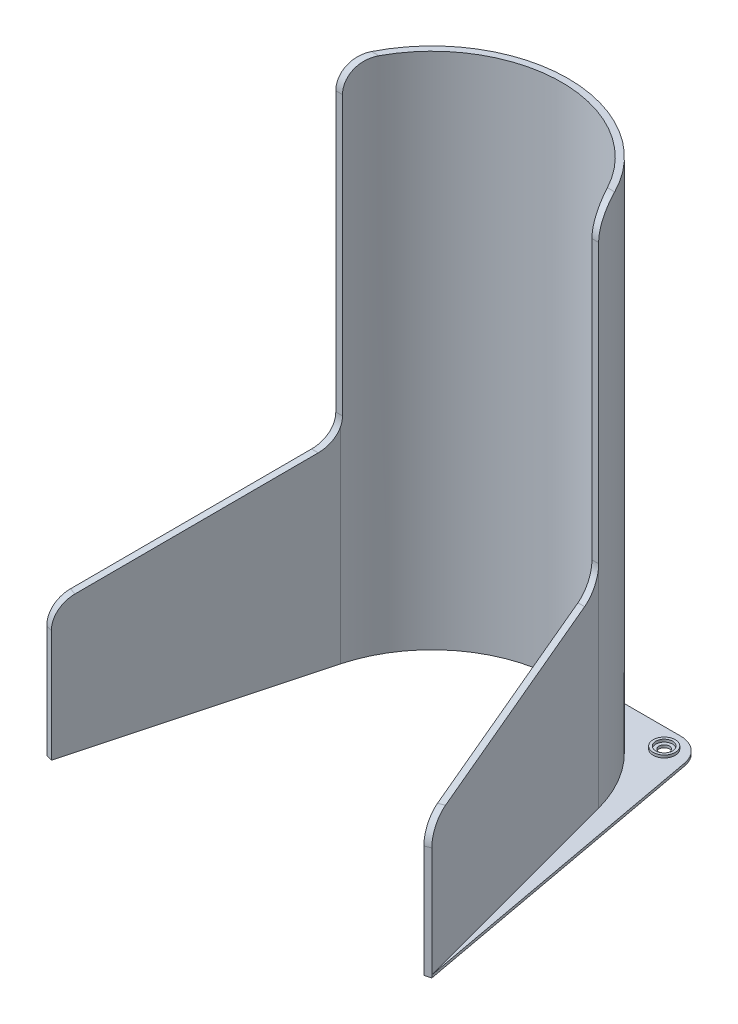
SolidWorks part; units mm, degrees
note: The reader was unsure of these and kept them because the rebuilt part matched: shared geometry of "Esquisse1<4>", "Esquisse1<6>".
ref_plane "Plan de face" through (0, 0, 0) normal (0, 0, 1) x (1, 0, 0)
ref_plane "Plan de dessus" through (0, 0, 0) normal (0, 1, 0) x (1, 0, 0)
ref_plane "Plan de droite" through (0, 0, 0) normal (1, 0, 0) x (0, 0, -1)
sketch "Esquisse1" plane through (0, 0, 0) normal (0, 1, 0) x (1, 0, 0)
  line L0 (0, 90) -> (0, 100) construction
  line L1 (-96.5926, 25.8819) -> (-143.72, -150)
  line L2 (143.72, -150) -> (-143.72, -150) construction
  line L3 (0, -150) -> (0, -100) construction
  line L4 (0, -90) -> (0, 0) construction
  line L5 (0, -100) -> (0, -90) construction
  line L6 (-143.72, -150) -> (-148.5496, -148.7059)
  line L7 (-148.5496, -148.7059) -> (-101.4222, 27.176)
  line L8 (0, 100) -> (0, 105) construction
  line L9 (-96.5926, 25.8819) -> (-101.4222, 27.176) construction
  line L10 (-148.5496, -148.7059) -> (-101.4222, 106.9873)
  line L11 (0, 105) -> (0, 106.9873) construction
  line L12 (-101.4222, 106.9873) -> (0, 0) construction
  line L13 (101.4222, 106.9873) -> (-101.4222, 106.9873)
  line L14 (-101.4222, 27.176) -> (-101.4222, 106.9873) construction
  line L15 (101.4222, 27.176) -> (101.4222, 106.9873) construction
  line L16 (101.4222, 106.9873) -> (0, 0) construction
  line L17 (148.5496, -148.7059) -> (101.4222, 106.9873)
  line L18 (148.5496, -148.7059) -> (101.4222, 27.176)
  line L19 (143.72, -150) -> (148.5496, -148.7059)
  line L20 (96.5926, 25.8819) -> (143.72, -150)
  arc A0 (0, 90) -> (0, -90) centre (0, 0) ccw construction
  arc A1 (96.5926, 25.8819) -> (-96.5926, 25.8819) centre (0, 0) ccw
  arc A2 (-96.5926, 25.8819) -> (0, -100) centre (0, 0) ccw construction
  arc A3 (-101.4222, 27.176) -> (101.4222, 27.176) centre (0, 0) cw
  circle A4 centre (-87.2025, 91.9873) radius 6.5
  circle A5 centre (-87.2025, 91.9873) radius 8.5
  circle A6 centre (87.2025, 91.9873) radius 8.5
  circle A7 centre (87.2025, 91.9873) radius 6.5
  circle A8 centre (-87.2025, 91.9873) radius 4
  circle A9 centre (87.2025, 91.9873) radius 4
  dimension "D1" = 180
  dimension "D7" = 13
  dimension "D9" = 2
  dimension "D2" = 8
  dimension "D3" = 15
  dimension "D4" = 5
  dimension "D5" = 174.4049
  dimension "D6" = 50
  dimension "D10" = 260
  dimension "D11" = 15
extrude "Boss.-Extru.1" add sketch "Esquisse1" along normal blind 2 contours A3 L7 L6 L1 A1 L20 L19 L18 | L7 A3 L18 L17 L13 L10 A5 A6 | A5 A4 | A4 A8 | A7 A9
extrude "Boss.-Extru.2" add sketch "Esquisse1<4>" along normal blind 400 contours A3 L7 L6 L1 A1 L20 L19 L18
sketch "Esquisse1<4>" plane through (0, 0, 0) normal (0, 1, 0) x (1, 0, 0) same geometry as "Esquisse1"
sketch "Esquisse2" plane through (0, 0, 0) normal (1, 0, 0) x (0, 0, -1)
  line L0 (27.176, 400) -> (27.176, 2) construction
  line L4 (-148.7059, 2) -> (-148.7059, 400) construction
  line L6 (27.176, 150) -> (27.176, 0)
  line L12 (-150, 101.9916) -> (27.176, 150)
  line L13 (-150, 596.5165) -> (27.176, 596.5165)
  line L14 (27.176, 596.5165) -> (27.176, 150)
  line L15 (-150, 400) -> (-150, 0) construction
  line L17 (-150, 596.5165) -> (-150, 0)
  line L19 (25.8819, 0) -> (-150, 0) construction
  line L20 (27.176, 0) -> (-150, 0)
  point P10 (-148.7059, 634.1962)
  point P11 (-150, 101.9916)
  point P12 (27.176, 0)
  point P14 (28.0155, 0)
  point P15 (27.417, 0)
  point P17 (-150, 596.5165)
  point P18 (-150, 600.6095)
  dimension "D1" = 100
  dimension "D2" = 150
extrude "Enlèv. mat.-Extru.1" cut sketch "Esquisse2" against normal up to next and the other way up to next
fillet "Congé1" radius 20 8 edges at (98.8294, 400, -27.176) (-98.8294, 400, -27.176) (-146.1348, 102.167, 149.353) (146.1348, 102.167, 149.353) (98.8294, 150, -27.176) (-98.8294, 150, -27.176) (-101.4222, 1, -106.9873) (101.4222, 1, -106.9873)
extrude "Boss.-Extru.4" add sketch "Esquisse1<6>" along normal blind 4 contours A5 A4 | A6 A7
sketch "Esquisse1<6>" plane through (0, 0, 0) normal (0, 1, 0) x (1, 0, 0) same geometry as "Esquisse1"
scale "Echelle1/2" scale about centroid uniform scaling yes scale factor 0.5
